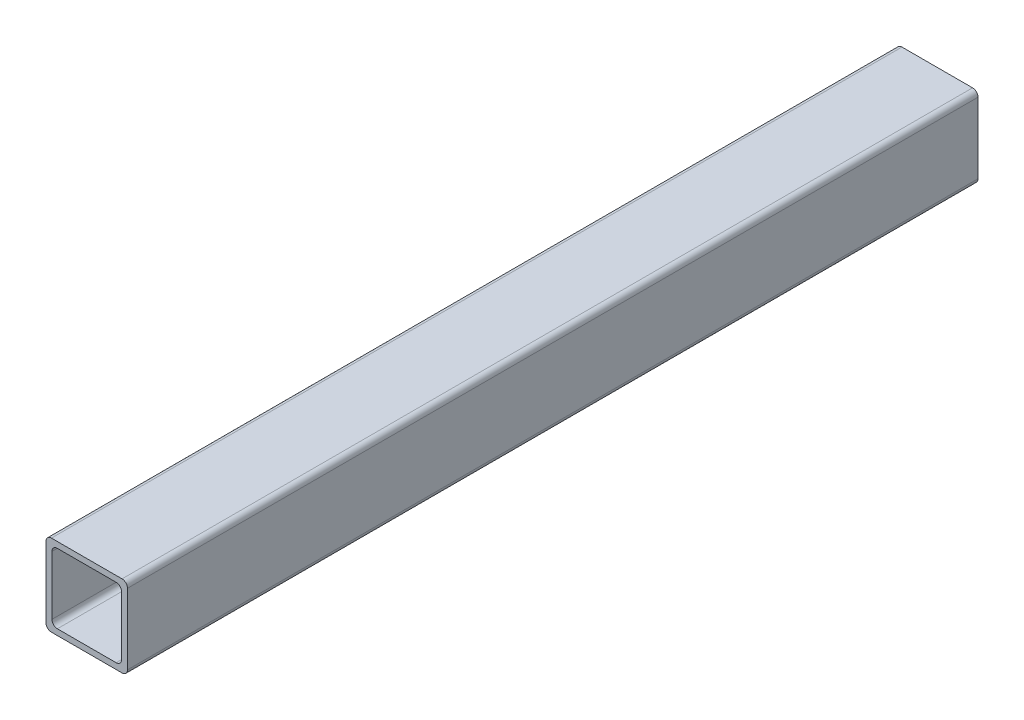
SolidWorks part; units mm, degrees
material "ASTM A500 Grade B Steel"
ref_plane "Front Plane" through (0, 0, 0) normal (0, 0, 1) x (1, 0, 0)
ref_plane "Top Plane" through (0, 0, 0) normal (0, 1, 0) x (1, 0, 0)
ref_plane "Right Plane" through (0, 0, 0) normal (1, 0, 0) x (0, 0, -1)
sketch "Sketch1" plane through (0, 0, 0) normal (0, 0, 1) x (1, 0, 0)
  line L0 (5.3086, -2.7686) -> (32.7914, -2.7686)
  line L1 (2.54, 0) -> (35.56, 0)
  line L2 (0, -2.54) -> (0, -35.56)
  line L3 (2.54, -38.1) -> (35.56, -38.1)
  line L4 (38.1, -2.54) -> (38.1, -35.56)
  line L5 (35.3314, -5.3086) -> (35.3314, -32.7914)
  line L6 (5.3086, -35.3314) -> (32.7914, -35.3314)
  line L7 (2.7686, -5.3086) -> (2.7686, -32.7914)
  line L8 (0, 0) -> (0, -38.1) construction
  line L9 (0, -38.1) -> (38.1, -38.1) construction
  line L10 (38.1, 0) -> (38.1, -38.1) construction
  line L11 (2.7686, -2.7686) -> (2.7686, -35.3314) construction
  line L12 (2.7686, -35.3314) -> (35.3314, -35.3314) construction
  line L13 (35.3314, -2.7686) -> (35.3314, -35.3314) construction
  line L14 (2.7686, -2.7686) -> (35.3314, -2.7686) construction
  line L15 (0, 0) -> (38.1, 0) construction
  arc A0 (0, -35.56) -> (2.54, -38.1) centre (2.54, -35.56) ccw
  arc A1 (38.1, -35.56) -> (35.56, -38.1) centre (35.56, -35.56) cw
  arc A2 (2.7686, -32.7914) -> (5.3086, -35.3314) centre (5.3086, -32.7914) ccw
  arc A3 (32.7914, -35.3314) -> (35.3314, -32.7914) centre (32.7914, -32.7914) ccw
  arc A4 (35.3314, -5.3086) -> (32.7914, -2.7686) centre (32.7914, -5.3086) ccw
  arc A5 (38.1, -2.54) -> (35.56, 0) centre (35.56, -2.54) ccw
  arc A6 (0, -2.54) -> (2.54, 0) centre (2.54, -2.54) cw
  arc A7 (5.3086, -2.7686) -> (2.7686, -5.3086) centre (5.3086, -5.3086) ccw
  point P12 (0, -38.1)
  dimension "D4" = 2.54
  dimension "D3" = 2.7686
extrude "Boss-Extrude1" add sketch "Sketch1" along normal blind 397
sketch "Sketch2" plane through (0, 0, 0) normal (0, 0, -1) x (-1, 0, 0)
  line L0 (-32.7914, -2.7686) -> (-5.3086, -2.7686) construction
  line L1 (-32.7914, -2.7686) -> (-5.3086, -2.7686)
  line L2 (-2.7686, -5.3086) -> (-2.7686, -32.7914) construction
  line L3 (-2.7686, -5.3086) -> (-2.7686, -32.7914)
  line L4 (0, -35.56) -> (0, -2.54)
  line L5 (-2.54, 0) -> (-35.56, 0)
  line L6 (-38.1, -2.54) -> (-38.1, -35.56)
  line L7 (-35.56, -38.1) -> (-2.54, -38.1)
  line L8 (0, -35.56) -> (0, -2.54)
  line L9 (-2.54, 0) -> (-35.56, 0)
  line L10 (-38.1, -2.54) -> (-38.1, -35.56)
  line L11 (-35.56, -38.1) -> (-2.54, -38.1)
  line L12 (-35.3314, -32.7914) -> (-35.3314, -5.3086) construction
  line L13 (-5.3086, -35.3314) -> (-32.7914, -35.3314) construction
  line L14 (-35.3314, -32.7914) -> (-35.3314, -5.3086)
  line L15 (-5.3086, -35.3314) -> (-32.7914, -35.3314)
  arc A0 (-2.7686, -5.3086) -> (-5.3086, -2.7686) centre (-5.3086, -5.3086) ccw construction
  arc A1 (-2.7686, -5.3086) -> (-5.3086, -2.7686) centre (-5.3086, -5.3086) ccw
  arc A2 (-32.7914, -2.7686) -> (-35.3314, -5.3086) centre (-32.7914, -5.3086) ccw construction
  arc A3 (-35.3314, -32.7914) -> (-32.7914, -35.3314) centre (-32.7914, -32.7914) ccw construction
  arc A4 (-2.54, -38.1) -> (0, -35.56) centre (-2.54, -35.56) ccw
  arc A5 (0, -2.54) -> (-2.54, 0) centre (-2.54, -2.54) ccw
  arc A6 (-35.56, 0) -> (-38.1, -2.54) centre (-35.56, -2.54) ccw
  arc A7 (-38.1, -35.56) -> (-35.56, -38.1) centre (-35.56, -35.56) ccw
  arc A8 (-2.54, -38.1) -> (0, -35.56) centre (-2.54, -35.56) ccw
  arc A9 (0, -2.54) -> (-2.54, 0) centre (-2.54, -2.54) ccw
  arc A10 (-35.56, 0) -> (-38.1, -2.54) centre (-35.56, -2.54) ccw
  arc A11 (-38.1, -35.56) -> (-35.56, -38.1) centre (-35.56, -35.56) ccw
  arc A12 (-5.3086, -35.3314) -> (-2.7686, -32.7914) centre (-5.3086, -32.7914) ccw construction
  arc A13 (-32.7914, -2.7686) -> (-35.3314, -5.3086) centre (-32.7914, -5.3086) ccw
  arc A14 (-35.3314, -32.7914) -> (-32.7914, -35.3314) centre (-32.7914, -32.7914) ccw
  arc A15 (-5.3086, -35.3314) -> (-2.7686, -32.7914) centre (-5.3086, -32.7914) ccw
  dimension "D1" = 0
extrude "Boss-Extrude2" add sketch "Sketch2" along normal up to surface (0.6787 mm away)
